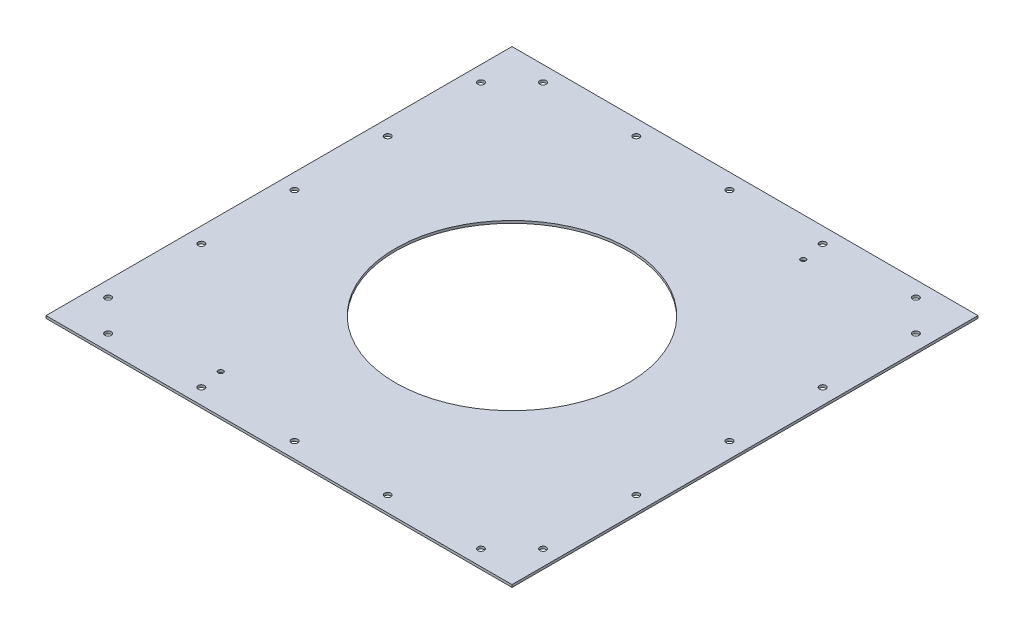
SolidWorks part; units mm, degrees
ref_plane "Front Plane" through (0, 0, 0) normal (0, 0, 1) x (1, 0, 0)
ref_plane "Top Plane" through (0, 0, 0) normal (0, 1, 0) x (1, 0, 0)
ref_plane "Right Plane" through (0, 0, 0) normal (1, 0, 0) x (0, 0, -1)
sketch "Sketch1" plane through (0, 0, 0) normal (0, 1, 0) x (1, 0, 0)
  line L1 (-300, -300) -> (300, -300)
  line L2 (-300, -300) -> (-300, 300)
  line L3 (-300, 300) -> (300, 300)
  line L4 (300, -300) -> (300, 300)
  line L5 (-300, -300) -> (300, 300) construction
  line L6 (-300, 300) -> (300, -300) construction
  circle A4 centre (125, 250) radius 3.25
  circle A5 centre (-125, -250) radius 3.25
  circle A6 centre (0, 0) radius 150
  point P0 (0, 0)
  dimension "D5" = 300
  dimension "D6" = 6.5
  dimension "D7" = 6.5
  dimension "D1" = 45
  dimension "D2" = 600
extrude "Boss-Extrude1" add sketch "Sketch1" along normal blind 1.5875 and the other way blind 1.5875
sketch "Sketch3" plane through (0, 0, 0) normal (0, 1, 0) x (1, 0, 0)
  line L0 (0, 300) -> (0, 280) construction
  line L1 (300, 300) -> (-300, 300) construction
  line L2 (0, -55) -> (0, 55) construction
  circle A0 centre (0, 280) radius 4.1
  circle A1 centre (-120, 280) radius 4.1
  circle A2 centre (-240, 280) radius 4.1
  circle A3 centre (240, 280) radius 4.1
  circle A4 centre (120, 280) radius 4.1
  dimension "D2" = 3
  dimension "8" = 8.2
  dimension "D1" = 20
extrude "Cut-Extrude2" cut sketch "Sketch3" against normal through all both and the other way through all
ref_axis "Axis1" through (0, 1.7463, 0) along (0, -1, 0)
pattern_circular "CirPattern1" count 4 every 90 about axis through (0, 1.7463, 0) along (0, -1, 0) of "Cut-Extrude2"
